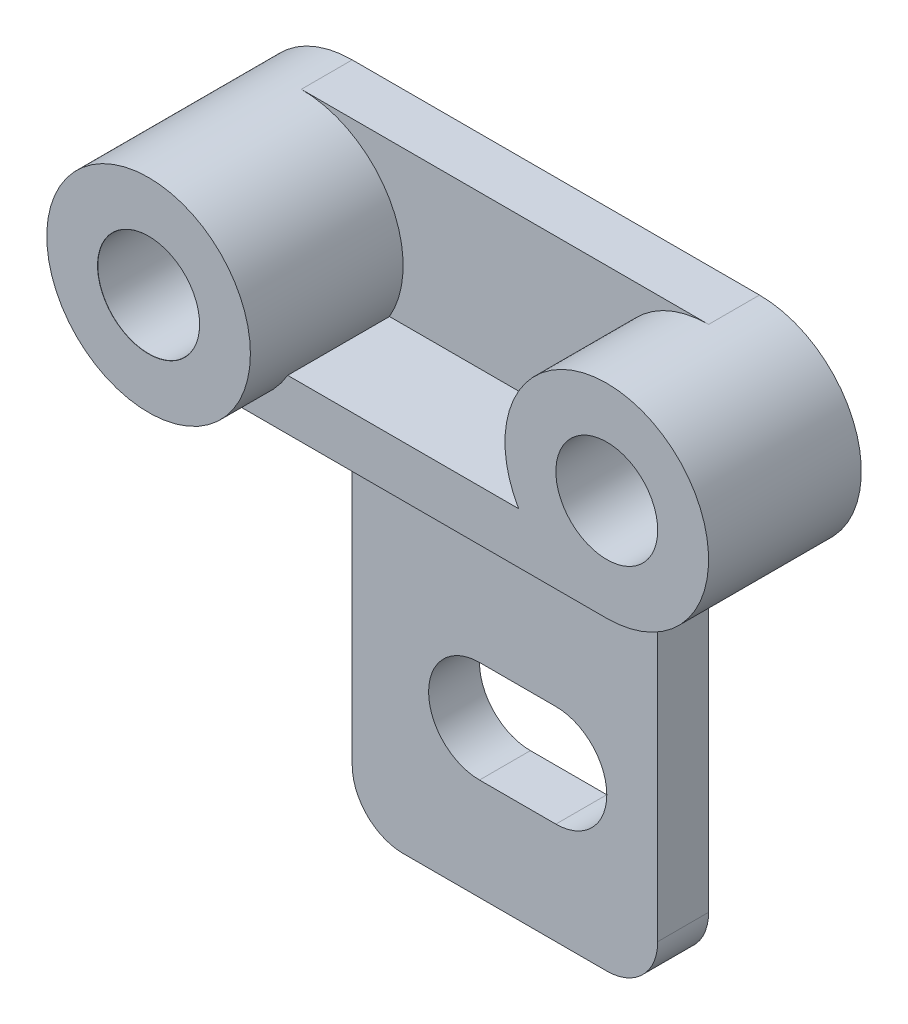
SolidWorks part; units mm, degrees
ref_plane "Front Plane" through (0, 0, 0) normal (0, 0, 1) x (1, 0, 0)
ref_plane "Top Plane" through (0, 0, 0) normal (0, 1, 0) x (1, 0, 0)
ref_plane "Right Plane" through (0, 0, 0) normal (1, 0, 0) x (0, 0, -1)
sketch "Sketch1" plane through (0, 0, 0) normal (0, 0, 1) x (1, 0, 0)
  circle A0 centre (-40, 0) radius 20
  circle A1 centre (40, 0) radius 20
  dimension "D1" = 40
  dimension "D2" = 40
  dimension "D3" = 40
  dimension "D4" = 80
extrude "Boss-Extrude1" add sketch "Sketch1" along normal blind 40 contours A0
extrude "Boss-Extrude2" add sketch "Sketch1<3>" along normal blind 30 separate body contours A1
sketch "Sketch1<3>" plane through (0, 0, 0) normal (0, 0, 1) x (1, 0, 0) same geometry as "Sketch1"
sketch "Sketch2" plane through (0, 0, 0) normal (0, 0, -1) x (-1, 0, 0)
  line L1 (-40, 20) -> (40, 20)
  line L2 (-40, 20) -> (-40, -20)
  line L3 (-40, -20) -> (40, -20)
  line L4 (40, 20) -> (40, -20)
  circle A0 centre (-40, 0) radius 20 construction
  circle A1 centre (40, 0) radius 20 construction
extrude "Boss-Extrude3" add sketch "Sketch2" against normal blind 10
sketch "Sketch3" plane through (0, 0, 30) normal (0, 0, 1) x (1, 0, 0)
  line L0 (40, -20) -> (-40, -20) construction
  line L1 (-40, -10) -> (40, -10)
  line L2 (-40, -10) -> (-40, -20)
  line L3 (-40, -20) -> (40, -20)
  line L4 (40, -10) -> (40, -20)
  dimension "D1" = 10
extrude "Boss-Extrude4" add sketch "Sketch3" against normal blind 30
sketch "Sketch4" plane through (0, 0, 0) normal (0, 0, -1) x (-1, 0, 0)
  line L0 (-40, -20) -> (40, -20) construction
  line L1 (-30, -20) -> (30, -20)
  line L2 (-30, -20) -> (-30, -90)
  line L3 (-20, -100) -> (20, -100)
  line L4 (30, -20) -> (30, -90)
  arc A0 (20, -100) -> (30, -90) centre (20, -90) ccw
  arc A1 (-30, -90) -> (-20, -100) centre (-20, -90) ccw
  point P10 (30, -100)
  point P13 (-30, -100)
  dimension "D4" = 10
  dimension "D1" = 60
  dimension "D2" = 100
  dimension "D3" = 30
extrude "Boss-Extrude5" add sketch "Sketch4" against normal blind 10
sketch "Sketch5" plane through (0, 0, 10) normal (0, 0, 1) x (1, 0, 0)
  line L0 (-5, -70) -> (10, -70) construction
  line L1 (-5, -60) -> (10, -60)
  line L2 (-5, -80) -> (10, -80)
  line L3 (20, -100) -> (-20, -100) construction
  line L4 (30, -20) -> (30, -90) construction
  arc A0 (-5, -60) -> (-5, -80) centre (-5, -70) ccw
  arc A1 (10, -80) -> (10, -60) centre (10, -70) ccw
  point P2 (2.5, -70)
  dimension "D2" = 10
  dimension "D1" = 15
  dimension "D3" = 30
  dimension "D4" = 20
extrude "Cut-Extrude1" cut sketch "Sketch5" against normal through all
hole_wizard "Ø20.0mm Dowel Hole1" positions "Sketch8" profile "Sketch9" hole size "Ø20.0" standard "ISO" end condition through all
sketch "Sketch8" plane through (0, 0, 40) normal (0, 0, 1) x (1, 0, 0)
  point P0 (-40, 0)
  point P3 (40, 0)
sketch "Sketch9" plane through (-40, 0, 40) normal (1, 0, 0) x (0, -1, 0)
  line L0 (0, 0) -> (0, 40)
  line L1 (0, 40) -> (10, 40)
  line L2 (10, 40) -> (10, 0.021)
  line L3 (10, 0.021) -> (10.025, 0)
  line L5 (10.025, 0) -> (0, 0)
  line L6 (-10, 0.021) -> (-10.025, 0) construction
  line L11 (0, -6.35) -> (0, 107.95) construction
  dimension "Thru Hole Dia." = 20
  dimension "Thru Hole Depth" = 40
  dimension "Near C'Sink Dia." = 20.05
  dimension "Near C'Sink Angle" = 100
